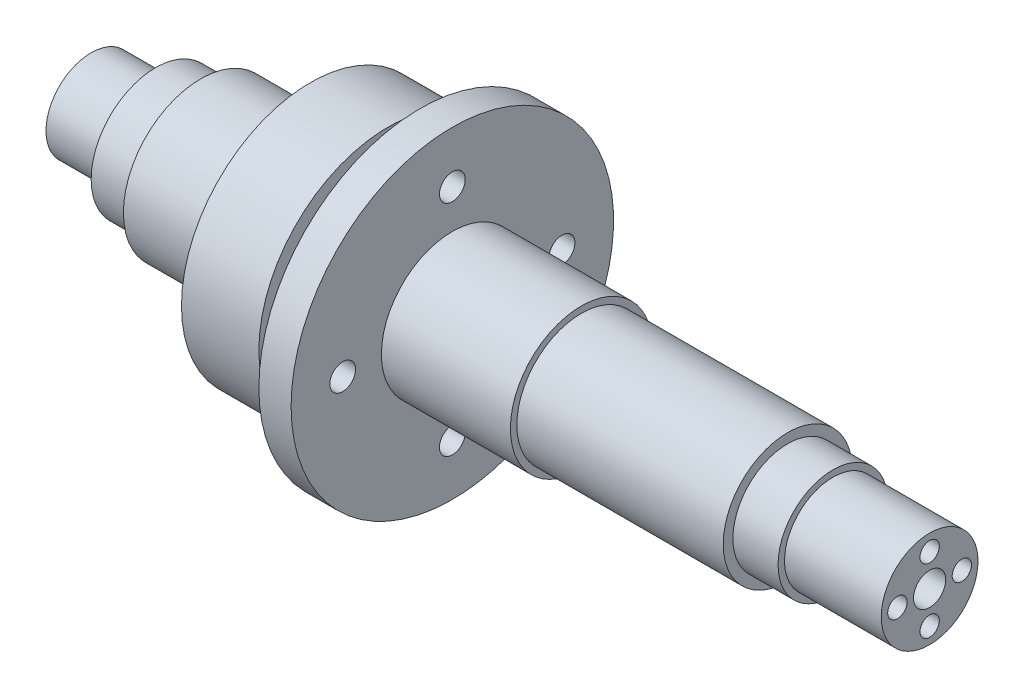
SolidWorks part; units mm, degrees
ref_plane "Front Plane" through (0, 0, 0) normal (0, 0, 1) x (1, 0, 0)
ref_plane "Top Plane" through (0, 0, 0) normal (0, 1, 0) x (1, 0, 0)
ref_plane "Right Plane" through (0, 0, 0) normal (1, 0, 0) x (0, 0, -1)
other "Center of Mass"
sketch "Sketch3" plane through (0, 0, 0) normal (0, 0, 1) x (1, 0, 0)
  line L0 (0, 0) -> (0, 39.0464) construction
  line L1 (-72.5, 0) -> (72.5, 0) construction
  line L2 (-72.5, 2.5) -> (-72.5, 0) construction
  line L3 (-72.5, 2.5) -> (-72.5, 7)
  line L4 (-72.5, 7) -> (-62.5, 7)
  line L5 (-62.5, 7) -> (-62.5, 10)
  line L6 (-62.5, 10) -> (-55.5, 10)
  line L7 (-55.5, 10) -> (-55.5, 12)
  line L8 (-55.5, 12) -> (-38.5, 12)
  line L9 (-38.5, 12) -> (-38.5, 20)
  line L10 (-38.5, 20) -> (-26.5, 20)
  line L11 (-26.5, 20) -> (-26.5, 11)
  line L12 (-26.5, 11) -> (-21.5, 11)
  line L13 (3.5, 11) -> (3.5, 10)
  line L14 (3.5, 10) -> (35.5, 10)
  line L15 (35.5, 10) -> (35.5, 8.5)
  line L17 (72.5, 7.5) -> (72.5, 2.5)
  line L18 (72.5, 2.5) -> (-72.5, 2.5)
  line L19 (-32.5, 20) -> (-32.5, 2.5) construction
  line L20 (-11.5, 11) -> (-11.5, 2.5) construction
  line L21 (-77.5, 12) -> (-72.8417, 12) construction
  line L22 (-62.5, 10) -> (-62.5, 16) construction
  line L23 (-77.5, 15) -> (-72.8417, 15) construction
  line L24 (35.5, 8.5) -> (42.5, 8.5)
  line L25 (11.9511, 11) -> (20.8732, 11) construction
  line L26 (30.861, 12) -> (33.3773, 12) construction
  line L27 (42.5, 8.5) -> (42.5, 7.5)
  line L36 (42.5, 7.5) -> (72.5, 7.5)
  line L37 (-21.5, 11) -> (-21.5, 25)
  line L38 (35.5, 8.5) -> (44.5, 8.5) construction
  line L39 (-21.5, 25) -> (-16.5, 25)
  line L40 (-16.5, 25) -> (-16.5, 11)
  line L42 (-16.5, 11) -> (3.5, 11)
  point P5 (0, 0)
  dimension "D3" = 40
  dimension "D2" = 22
  dimension "D4" = 40
  dimension "D5" = 12
  dimension "D6" = 10
  dimension "D7" = 7
  dimension "D9" = 5
  dimension "D10" = 14
  dimension "D11" = 20
  dimension "D12" = 12
  dimension "D13" = 24
  dimension "D14" = 32
  dimension "D15" = 15
  dimension "D16" = 20
  dimension "D18" = 11
  dimension "D20" = 12
  dimension "D21" = 7
  dimension "D22" = 17
  dimension "D24" = 15
  dimension "D8" = 30
  dimension "D17" = 32
  dimension "D19" = 30
  dimension "D23" = 5
  dimension "D25" = 5
  dimension "D26" = 25
revolve "Revolve1" add sketch "Sketch3" angle 360 about L1
ref_plane "Plane1" through (0, 11, 0) normal (0, 1, 0) x (1, 0, 0)
sketch "Sketch4" plane through (0, 11, 0) normal (0, 1, 0) x (1, 0, 0)
  line L0 (3.5, 0) -> (-26.5, 0) construction
  line L1 (3.5, -11) -> (3.5, 11) construction
  line L2 (-26.5, -11) -> (-26.5, 11) construction
  line L3 (-11.5, 0) -> (-11.5, 23.5234) construction
  line L4 (72.5, -7.5) -> (72.5, 7.5) construction
  line L5 (72.5, 0) -> (62.5, 0) construction
  line L6 (-17.5, -2) -> (-5.5, -2)
  line L7 (-17.5, -2) -> (-17.5, 2)
  line L8 (-17.5, 2) -> (-5.5, 2)
  line L9 (-5.5, -2) -> (-5.5, 2)
  line L10 (-17.5, -2) -> (-5.5, 2) construction
  line L11 (-17.5, 2) -> (-5.5, -2) construction
  line L16 (56.5, -2) -> (68.5, -2)
  line L17 (56.5, -2) -> (56.5, 2)
  line L18 (56.5, 2) -> (68.5, 2)
  line L19 (68.5, -2) -> (68.5, 2)
  line L20 (56.5, -2) -> (68.5, 2) construction
  line L21 (56.5, 2) -> (68.5, -2) construction
  point P17 (62.5, 0)
  dimension "D1" = 12
  dimension "D2" = 4
  dimension "D3" = 10
  dimension "D4" = 12
  dimension "D5" = 4
fillet "Fillet1" radius 1 2 edges at (-26.5, 0, 11) (-38.5, 0, 12)
ref_plane "Plane2" through (0, 7.5, 0) normal (0, 1, 0) x (1, 0, 0)
sketch "Sketch5" plane through (0, 7.5, 0) normal (0, 1, 0) x (1, 0, 0)
  line L0 (68.5, -2) -> (68.5, 2) construction
  line L1 (56.5, -2) -> (68.5, -2) construction
  line L2 (56.5, -2) -> (56.5, 2) construction
  line L3 (56.5, 2) -> (68.5, 2) construction
  line L4 (68.5, -2) -> (68.5, 2)
  line L5 (56.5, -2) -> (68.5, -2)
  line L6 (56.5, -2) -> (56.5, 2)
  line L7 (56.5, 2) -> (68.5, 2)
sketch "Sketch6" [suppressed] plane through (0, 0, 0) normal (0, 0, 1) x (1, 0, 0)
  line L0 (-52.75, 0) -> (52.75, 0) construction
  line L1 (-52.75, 4.5) -> (-52.75, 7)
  line L2 (-52.75, 7) -> (-42.75, 7)
  line L3 (-42.75, 7) -> (-42.75, 10)
  line L4 (-42.75, 10) -> (-35.75, 10)
  line L5 (-35.75, 10) -> (-35.75, 12)
  line L6 (-35.75, 12) -> (-28.25, 12)
  line L7 (-28.25, 12) -> (-28.25, 11)
  line L8 (-28.25, 11) -> (-1.75, 11)
  line L9 (44.75, 11) -> (44.75, 8.5)
  line L10 (44.75, 8.5) -> (52.75, 8.5)
  line L11 (52.75, 8.5) -> (52.75, 4.5)
  line L12 (52.75, 4.5) -> (-52.75, 4.5)
  line L13 (8.25, 11) -> (8.25, 4.5) construction
  line L14 (-1.75, 11) -> (-1.75, 22)
  line L15 (-1.75, 22) -> (3.25, 22)
  line L16 (3.25, 22) -> (3.25, 11)
  line L17 (3.25, 11) -> (44.75, 11)
  point P4 (0, 0)
  dimension "D1" = 10
  dimension "D2" = 7
  dimension "D3" = 8
  dimension "D4" = 61
  dimension "D5" = 105.5
  dimension "D6" = 7
  dimension "D7" = 10
  dimension "D8" = 12
  dimension "D9" = 11
  dimension "D10" = 8.5
  dimension "D11" = 9
  dimension "D12" = 31.5
  dimension "D13" = 5
  dimension "D14" = 22
  dimension "D15" = 24.5
revolve "Revolve2" [suppressed] add sketch "Sketch6" angle 360 about L0
ref_plane "Plane3" [suppressed] through (0, 11, 0) normal (0, 1, 0) x (1, 0, 0)
sketch "Sketch8" plane through (-16.5, 0, 0) normal (1, 0, 0) x (0, 0, -1)
  line L0 (0, 0) -> (0, 17) construction
  circle A0 centre (0, 17) radius 2
  circle A1 centre (17, 0) radius 2
  circle A2 centre (0, -17) radius 2
  circle A3 centre (-17, 0) radius 2
  point P12 (0, 0)
  dimension "D1" = 4
  dimension "D3" = 17
  dimension "D4" = 17
  dimension "D5" = 34
  dimension "D2" = 4
extrude "Cut-Extrude5" cut sketch "Sketch8" against normal up to surface (5 mm away) up to face at (-21.5, 0, 11)
sketch "Sketch9" [suppressed] plane through (3.25, 0, 0) normal (1, 0, 0) x (0, 0, -1)
  line L0 (0, 0) -> (0, 17) construction
  circle A0 centre (0, 17) radius 2
  circle A1 centre (17, 0) radius 2
  circle A2 centre (0, -17) radius 2
  circle A3 centre (-17, 0) radius 2
  point P12 (0, 0)
  dimension "D1" = 4
  dimension "D2" = 17
  dimension "D4" = 17
  dimension "D5" = 17
  dimension "D3" = 4
extrude "Cut-Extrude6" [suppressed] cut sketch "Sketch9" against normal up to surface (5 mm away)
sketch "Sketch10" plane through (72.5, 0, 0) normal (1, 0, 0) x (0, 0, -1)
  circle A1 centre (0, 0) radius 7.5 construction
  circle A2 centre (0, 0) radius 7.5
extrude "Cut-Extrude7" cut sketch "Sketch10" against normal blind 15
sketch "Sketch11" plane through (57.5, 0, 0) normal (1, 0, 0) x (0, 0, -1)
  line L0 (0, 0) -> (0, 5) construction
  circle A0 centre (0, 5) radius 1.5
  circle A1 centre (5, 0) radius 1.5
  circle A2 centre (0, -5) radius 1.5
  circle A3 centre (-5, 0) radius 1.5
  point P12 (0, 0)
  dimension "D1" = 3
  dimension "D3" = 5
  dimension "D2" = 4
extrude "Cut-Extrude8" cut sketch "Sketch11" against normal blind 10
equation "\"mainShaft-D\"= 20mm"
equation "\"mainTrackGear-D\"= 40mm"
equation "\"D4@Sketch3\"=\"wormGearL-D\""
equation "\"D11@Sketch3\"=\"mainShaft-D\""
equation "\"mini-flipper-shaft-diameter\"= 26mm"
equation "\"mini-shaft-ring-groove-diam\"= 7.8mm"
equation "\"mini-shaft-ring-groove-width\"= 1mm"
equation "\"dtCoverPlate-DistFrom-GearCent\"= 73mm"
equation "\"wormGearShaft-L\"= \"dtCoverPlate-DistFrom-GearCent\" - 27.75 + 3.75"
equation "\"wormGearShaft-Dsmall\"= 6mm"
equation "\"wormGearShaft-Dworm\"= 12mm"
equation "\"wormL-D\" = 12mm"
equation "\"wormR-D\" = 15mm"
equation "\"wormGearL-D\" = 40mm"
equation "\"wormGearR-D\" = 50mm"
